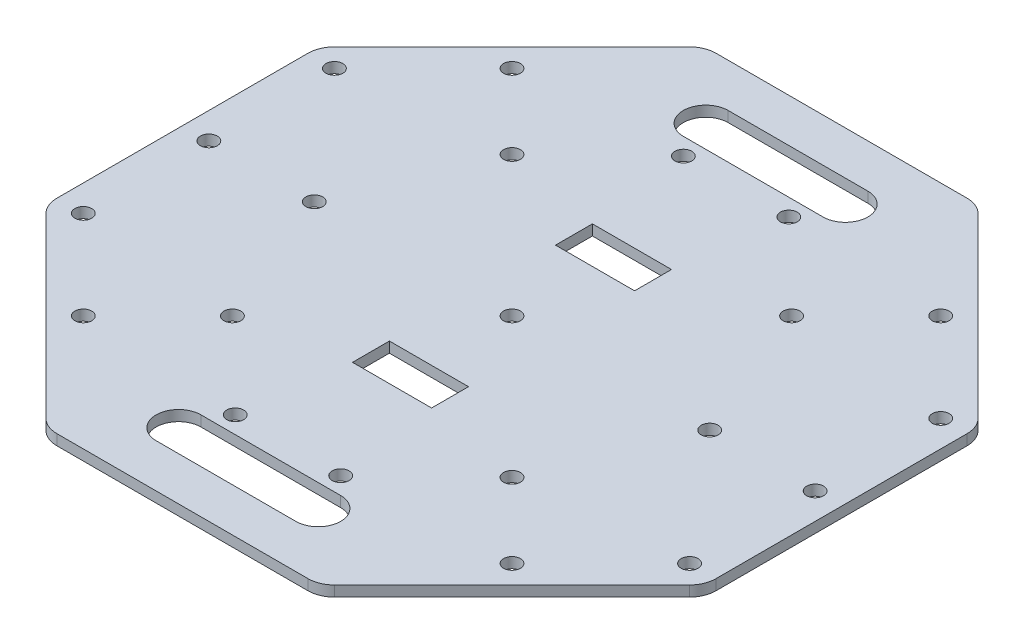
SolidWorks part; units mm, degrees
ref_plane "Front Plane" through (0, 0, 0) normal (0, 0, 1) x (1, 0, 0)
ref_plane "Top Plane" through (0, 0, 0) normal (0, 1, 0) x (1, 0, 0)
ref_plane "Right Plane" through (0, 0, 0) normal (1, 0, 0) x (0, 0, -1)
sketch "Sketch1" plane through (0, 0, 0) normal (0, 1, 0) x (1, 0, 0)
  line L0 (0, 67.6495) -> (0, -67.6495) construction
  line L1 (-67.6495, 0) -> (67.6495, 0) construction
  line L2 (62.5, 25.8883) -> (62.5, -25.8883)
  line L3 (-25.8883, 62.5) -> (25.8883, 62.5)
  line L4 (0, 0) -> (62.5, 25.8883) construction
  line L5 (-25.8883, 62.5) -> (0, 0) construction
  line L6 (-25.8883, -62.5) -> (25.8883, -62.5)
  line L7 (-62.5, 25.8883) -> (-62.5, -25.8883)
  line L8 (13.25, -50) -> (-13.25, -50) construction
  line L9 (13.25, -54.25) -> (-13.25, -54.25)
  line L10 (13.25, -45.75) -> (-13.25, -45.75)
  line L11 (13.25, 50) -> (-13.25, 50) construction
  line L12 (13.25, 54.25) -> (-13.25, 54.25)
  line L13 (13.25, 45.75) -> (-13.25, 45.75)
  line L14 (14.3249, -42.5) -> (-21.367, -42.5) construction
  line L15 (-7.5, -22.75) -> (7.5, -22.75)
  line L16 (-7.5, -22.75) -> (-7.5, -15.75)
  line L17 (-7.5, -15.75) -> (7.5, -15.75)
  line L18 (7.5, -22.75) -> (7.5, -15.75)
  line L19 (-7.5, -22.75) -> (7.5, -15.75) construction
  line L20 (-7.5, -15.75) -> (7.5, -22.75) construction
  line L21 (-7.5, 22.75) -> (-7.5, 15.75)
  line L22 (-7.5, 22.75) -> (7.5, 22.75)
  line L23 (7.5, 22.75) -> (7.5, 15.75)
  line L24 (-7.5, 15.75) -> (7.5, 15.75)
  line L25 (25.8883, -62.5) -> (62.5, -25.8883)
  line L26 (62.5, 25.8883) -> (25.8883, 62.5)
  line L27 (-25.8883, 62.5) -> (-62.5, 25.8883)
  line L28 (-62.5, -25.8883) -> (-25.8883, -62.5)
  circle A0 centre (0, 0) radius 67.6495
  arc A1 (13.25, -54.25) -> (13.25, -45.75) centre (13.25, -50) ccw
  arc A2 (-13.25, -45.75) -> (-13.25, -54.25) centre (-13.25, -50) ccw
  arc A3 (13.25, 54.25) -> (13.25, 45.75) centre (13.25, 50) cw
  arc A4 (-13.25, 45.75) -> (-13.25, 54.25) centre (-13.25, 50) cw
  circle A5 centre (10, -42.5) radius 1.6
  circle A6 centre (-10, -42.5) radius 1.6
  circle A7 centre (-10, 42.5) radius 1.6
  circle A8 centre (10, 42.5) radius 1.6
  point P17 (0, -50)
  point P24 (0, 50)
  point P29 (0, -19.25)
  dimension "D10" = 3.2
  dimension "D11" = 10
  dimension "D12" = 3.25
  dimension "D2" = 22.5
  dimension "D3" = 22.5
  dimension "D4" = 8.5
  dimension "D5" = 26.5
  dimension "D6" = 50
  dimension "D7" = 7
  dimension "D8" = 23
  dimension "D9" = 15
  dimension "D13" = 125
extrude "Boss-Extrude1" add sketch "Sketch1" along normal blind 2 contours L6 A0 L2 L3 L7 region at (0, 0, 0)
fillet "Fillet1" radius 5 8 edges at (-25.8883, 1, 62.5) (-62.5, 1, 25.8883) (-62.5, 1, -25.8883) (-25.8883, 1, -62.5) (25.8883, 1, -62.5) (62.5, 1, -25.8883) (62.5, 1, 25.8883) (25.8883, 1, 62.5)
sketch "Sketch2" plane through (0, 2, 0) normal (0, 1, 0) x (1, 0, 0)
  line L0 (62.5, 0) -> (-62.5, 0) construction
  line L1 (62.5, 23.8173) -> (62.5, -23.8173) construction
  line L2 (-62.5, 23.8173) -> (-62.5, -23.8173) construction
  line L3 (-44.1942, 44.1942) -> (44.1942, -44.1942) construction
  line L4 (-27.3528, 61.0355) -> (-61.0355, 27.3528) construction
  line L5 (27.3528, -61.0355) -> (61.0355, -27.3528) construction
  line L6 (44.1942, 44.1942) -> (-44.1942, -44.1942) construction
  line L7 (61.0355, 27.3528) -> (27.3528, 61.0355) construction
  line L8 (-61.0355, -27.3528) -> (-27.3528, -61.0355) construction
  line L9 (57.5, 30.8883) -> (57.5, -30.8883) construction
  line L10 (62.1194, 25.7307) -> (0, 0) construction
  line L11 (62.1194, -25.7307) -> (0, 0) construction
  line L12 (0, 62.5) -> (0, -62.5) construction
  line L13 (-23.8173, 62.5) -> (23.8173, 62.5) construction
  line L14 (-23.8173, -62.5) -> (23.8173, -62.5) construction
  circle A0 centre (57.5, 0) radius 1.6
  circle A1 centre (40.6586, -40.6586) radius 1.6
  circle A3 centre (-40.6586, -40.6586) radius 1.6
  circle A4 centre (-57.5, 0) radius 1.6
  circle A5 centre (-40.6586, 40.6586) radius 1.6
  circle A7 centre (40.6586, 40.6586) radius 1.6
  circle A8 centre (0, 57.5) radius 1.6 [skipped]
  circle A9 centre (0, -57.5) radius 1.6 [skipped]
  circle A10 centre (0, 0) radius 1.6
  circle A11 centre (37.5, 0) radius 1.6
  circle A12 centre (26.5165, -26.5165) radius 1.6
  circle A14 centre (-26.5165, -26.5165) radius 1.6
  circle A15 centre (-37.5, 0) radius 1.6
  circle A16 centre (-26.5165, 26.5165) radius 1.6
  circle A18 centre (26.5165, 26.5165) radius 1.6
  circle A19 centre (0, 37.5) radius 1.6 [skipped]
  circle A20 centre (0, -37.5) radius 1.6 [skipped]
  arc A21 (62.5, 23.8173) -> (61.0355, 27.3528) centre (57.5, 23.8173) ccw construction
  circle A22 centre (57.5, 23.8173) radius 1.6
  circle A23 centre (57.5, -23.8173) radius 1.6
  circle A24 centre (-57.5, -23.8173) radius 1.6
  circle A25 centre (-57.5, 23.8173) radius 1.6
  dimension "D1" = 3.2
  dimension "D2" = 5
  dimension "D4" = 3.2
  dimension "D5" = 3.2
  dimension "D6" = 25
  dimension "D8" = 3.2
  dimension "D3" = 8
  dimension "D7" = 8
extrude "Cut-Extrude1" cut sketch "Sketch2" against normal through all
